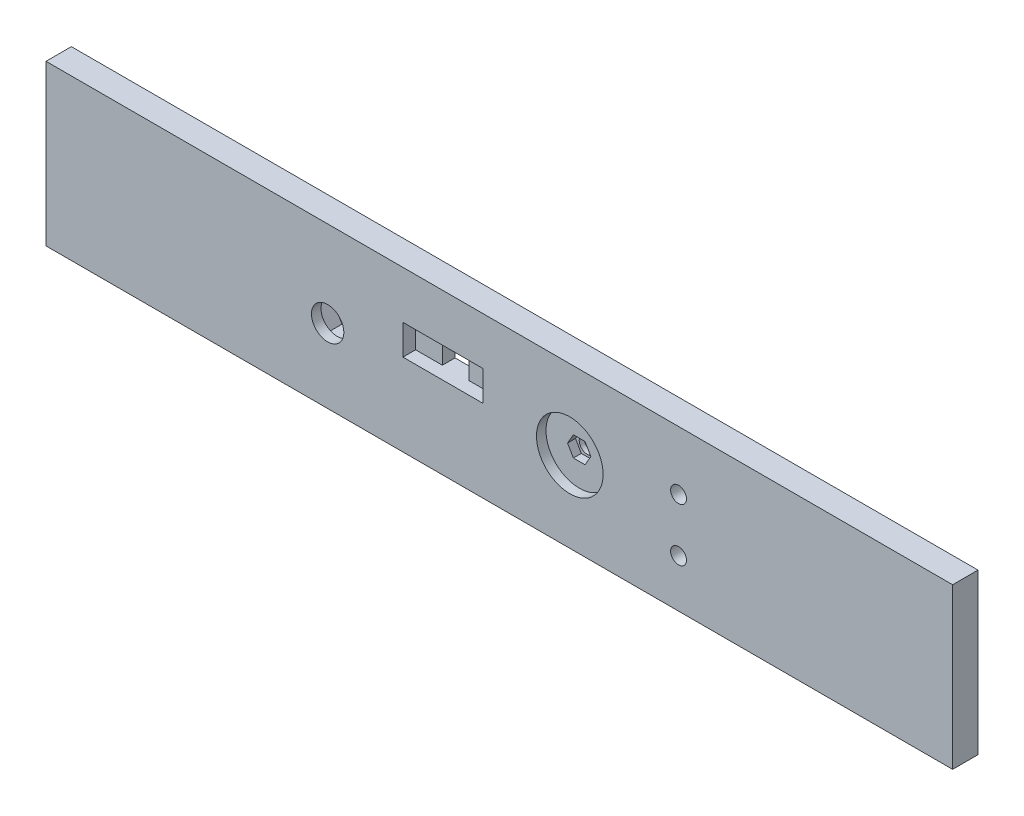
SolidWorks part; units mm, degrees
ref_plane "Front Plane" through (0, 0, 0) normal (0, 0, 1) x (1, 0, 0)
ref_plane "Top Plane" through (0, 0, 0) normal (0, 1, 0) x (1, 0, 0)
ref_plane "Right Plane" through (0, 0, 0) normal (1, 0, 0) x (0, 0, -1)
sketch "Sketch1" plane through (0, 0, 0) normal (0, 0, 1) x (1, 0, 0)
  line L1 (0, 0) -> (571.5, 0)
  line L2 (0, 0) -> (0, 100.8)
  line L3 (0, 100.8) -> (571.5, 100.8)
  line L4 (571.5, 0) -> (571.5, 100.8)
  dimension "D1" = 100.8
  dimension "D2" = 571.5
extrude "Boss-Extrude1" add sketch "Sketch1" along normal mid plane 16
sketch "Sketch4" plane through (0, 0, -8) normal (0, 0, -1) x (-1, 0, 0)
  line L3 (-571.5, 100.8) -> (0, 100.8) construction
  circle A0 centre (-330.1236, 50.8) radius 7.5
  dimension "D3" = 15
  dimension "D1" = 50
extrude "Cut-Extrude3" cut sketch "Sketch4" against normal blind 2
sketch "Sketch5" plane through (0, 0, -6) normal (0, 0, -1) x (-1, 0, 0)
  circle A0 centre (-330.1236, 50.8) radius 5
  dimension "D1" = 10
extrude "Cut-Extrude4" cut sketch "Sketch5" against normal through all
sketch "Sketch6" plane through (0, 0, 8) normal (0, 0, 1) x (1, 0, 0)
  line L1 (337.4675, 50.8) -> (333.7956, 57.16)
  line L2 (333.7956, 57.16) -> (326.4517, 57.16)
  line L3 (326.4517, 57.16) -> (322.7797, 50.8)
  line L4 (322.7797, 50.8) -> (326.4517, 44.44)
  line L5 (326.4517, 44.44) -> (333.7956, 44.44)
  line L6 (333.7956, 44.44) -> (337.4675, 50.8)
  circle A0 centre (330.1236, 50.8) radius 6.36 construction
  dimension "D1" = 12.72
extrude "Cut-Extrude5" cut sketch "Sketch6" against normal blind 11
sketch "Sketch9" plane through (0, 0, 8) normal (0, 0, 1) x (1, 0, 0)
  circle A0 centre (177.5367, 46.6) radius 10.2
  circle A1 centre (398.7408, 63.7028) radius 5
  circle A2 centre (398.7408, 30.252) radius 5
  dimension "D1" = 20.4
  dimension "D2" = 10
  dimension "D3" = 10
extrude "power and usb cables" cut sketch "Sketch9" against normal through all
sketch "Sketch10" plane through (0, 0, 8) normal (0, 0, 1) x (1, 0, 0)
  circle A0 centre (330.1639, 50.8218) radius 21
extrude "Cut-Extrude6" cut sketch "Sketch10" against normal blind 6
sketch "Sketch12" plane through (0, 0, -8) normal (0, 0, -1) x (-1, 0, 0)
  line L0 (-164.3354, 47.7347) -> (-169.9534, 57.4654) construction
  line L1 (-163.6803, 46.6) -> (-170.6085, 58.6)
  line L2 (-170.6085, 58.6) -> (-184.4649, 58.6)
  line L3 (-184.4649, 58.6) -> (-191.3931, 46.6)
  line L4 (-191.3931, 46.6) -> (-184.4649, 34.6)
  line L5 (-184.4649, 34.6) -> (-170.6085, 34.6)
  line L6 (-170.6085, 34.6) -> (-163.6803, 46.6)
  circle A0 centre (-177.5367, 46.6) radius 12 construction
  dimension "D1" = 0
extrude "Cut-Extrude8" cut sketch "Sketch12" against normal blind 10
sketch "Sketch13" plane through (0, 0, -8) normal (0, 0, -1) x (-1, 0, 0)
  line L0 (-275.4, 70.8) -> (-225, 70.8) construction
  line L1 (-258.55, 70.8) -> (-241.85, 70.8)
  line L2 (-258.55, 70.8) -> (-258.55, 51.8)
  line L3 (-258.55, 51.8) -> (-241.85, 51.8)
  line L4 (-241.85, 70.8) -> (-241.85, 51.8)
  line L5 (-225, 51.8) -> (-275.4, 51.8) construction
  circle A0 centre (-243.85, 68.92) radius 0.255 construction
  circle A1 centre (-256.55, 68.92) radius 0.255 construction
  dimension "D1" = 2
  dimension "D2" = 2
extrude "Cut-Extrude9" cut sketch "Sketch13" against normal through all and the other way through all
sketch "Sketch14" plane through (0, 0, 8) normal (0, 0, 1) x (1, 0, 0)
  line L1 (225, 70.8) -> (275.4, 70.8)
  line L2 (225, 70.8) -> (225, 51.8)
  line L3 (225, 51.8) -> (275.4, 51.8)
  line L4 (275.4, 70.8) -> (275.4, 51.8)
extrude "Cut-Extrude10" cut sketch "Sketch14" against normal blind 8
